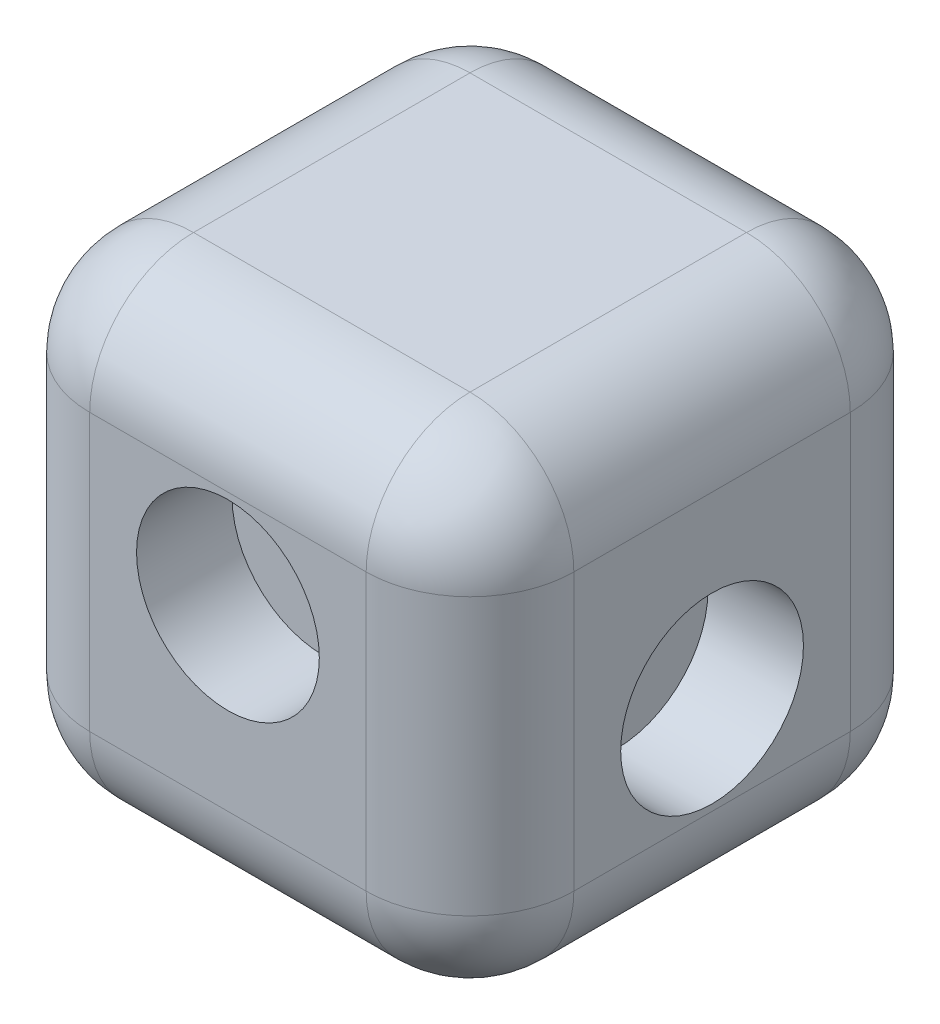
SolidWorks part; units mm, degrees
material "ASTM A36 Steel"
ref_plane "Front Plane" through (0, 0, 0) normal (0, 0, 1) x (1, 0, 0)
ref_plane "Top Plane" through (0, 0, 0) normal (0, 1, 0) x (1, 0, 0)
ref_plane "Right Plane" through (0, 0, 0) normal (1, 0, 0) x (0, 0, -1)
sketch "Sketch1" plane through (0, 0, 0) normal (0, 0, 1) x (1, 0, 0)
  line L1 (-14.8019, 14.8018) -> (14.8018, 14.8018)
  line L2 (-14.8019, 14.8018) -> (-14.8018, -14.8019)
  line L3 (-14.8018, -14.8019) -> (14.8019, -14.8019)
  line L4 (14.8018, 14.8018) -> (14.8019, -14.8019)
  line L5 (-14.8019, 14.8018) -> (14.8019, -14.8019) construction
  line L6 (-14.8018, -14.8019) -> (14.8018, 14.8018) construction
  point P0 (0, 0)
  dimension "D1" = 29.6037
  dimension "D2" = 29.6037
extrude "Boss-Extrude1" add sketch "Sketch1" along normal blind 14.8018 and the other way blind 14.8018
sketch "Sketch2" plane through (0, 0, 0) normal (0, 0, 1) x (1, 0, 0)
  line L2 (-14.8018, -14.8019) -> (14.8019, -14.8019) construction
  circle A1 centre (0, 2.4701) radius 5.588
  dimension "D1" = 17.272
sketch "Sketch3" plane through (-14.8019, 0, 0) normal (-1, 0, 0) x (0, 0, 1)
  line L1 (-14.8018, 14.8018) -> (14.8018, 14.8018) construction
  circle A0 centre (0, -2.4702) radius 5.588
  point P4 (0, 14.8018)
  dimension "D1" = 17.272
fillet "Fillet3" radius 6.35 1 edges at (14.8018, 14.8018, 0) type face fillet first side face at (0, 14.8018, 0) second side face at (14.8018, 0, 0)
fillet "Fillet4" radius 6.35 1 edges at (-14.8019, 14.8018, 0) type face fillet first side face at (-3.175, 14.8018, 0) second side face at (-14.8019, 0, 0)
fillet "Fillet5" radius 6.35 1 edges at (-14.8018, -14.8019, 0) type face fillet first side face at (-14.8019, -3.175, 0) second side face at (0, -14.8019, 0)
fillet "Fillet6" radius 6.35 1 edges at (14.8019, -14.8019, 0) type face fillet first side face at (14.8018, -3.175, 0) second side face at (3.175, -14.8019, 0)
sketch "Sketch7" plane through (0, 0, -14.8018) normal (0, 0, -1) x (-1, 0, 0)
  circle A0 centre (0, 2.4701) radius 5.588
extrude "Cut-Extrude3" cut sketch "Sketch7" against normal blind 5.842
sketch "Sketch8" plane through (0, 0, 14.8018) normal (0, 0, 1) x (1, 0, 0)
  circle A0 centre (0, 2.4701) radius 5.588
extrude "Cut-Extrude4" cut sketch "Sketch8" against normal blind 5.842
extrude "Cut-Extrude5" cut sketch "Sketch3" against normal blind 5.842
sketch "Sketch9" plane through (14.8018, 0, 0) normal (1, 0, 0) x (0, 0, -1)
  line L0 (0, 8.0581) -> (0, -3.1179) construction
  line L1 (-14.8018, 14.8018) -> (14.8018, 14.8018) construction
  circle A0 centre (0, -2.4702) radius 5.588
  dimension "D1" = 17.272
extrude "Cut-Extrude6" cut sketch "Sketch9" against normal blind 5.842
fillet "Fillet7" radius 6.35 1 edges at (0, 14.8018, 14.8018) type face fillet first side face at (5.588, 2.4701, 14.8018) second side face at (0, 14.8018, 0)
fillet "Fillet8" radius 6.35 1 edges at (0, 14.8018, -14.8018) type face fillet first side face at (-5.588, 2.4701, -14.8018) second side face at (0, 14.8018, -3.175)
